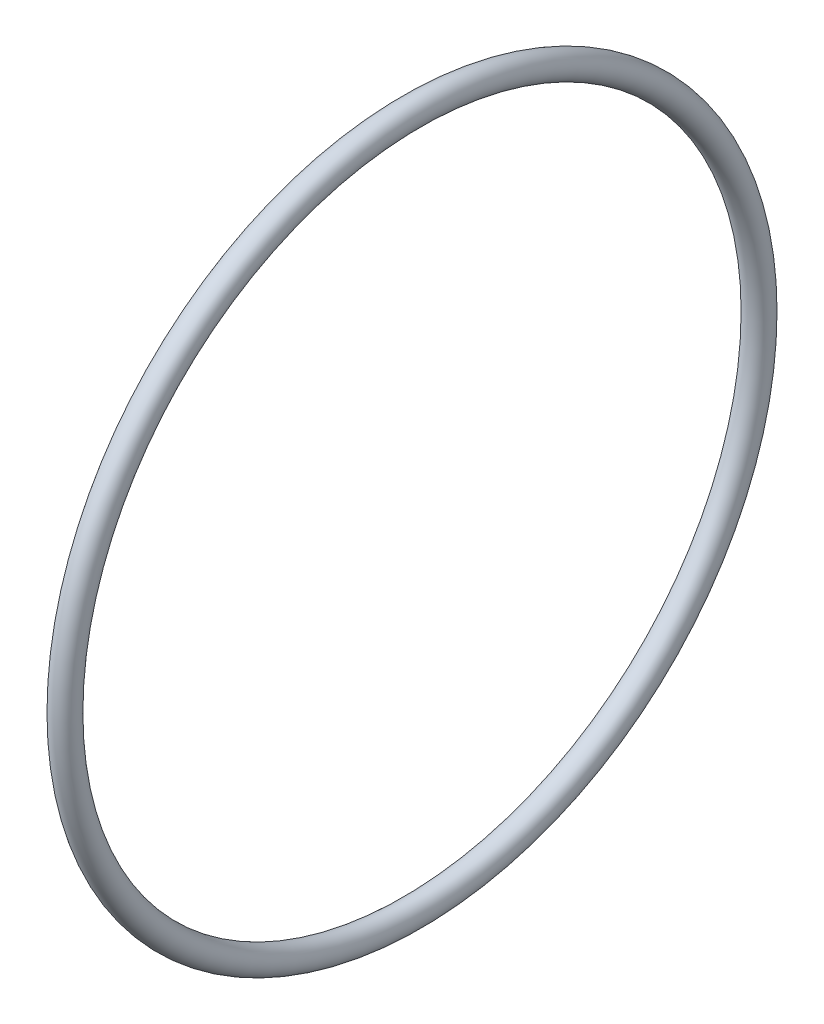
SolidWorks part; units mm, degrees
ref_plane "Front Plane" through (0, 0, 0) normal (0, 0, 1) x (1, 0, 0)
ref_plane "Top Plane" through (0, 0, 0) normal (0, 1, 0) x (1, 0, 0)
ref_plane "Right Plane" through (0, 0, 0) normal (1, 0, 0) x (0, 0, -1)
sketch "Sketch2" plane through (0, 0, 0) normal (0, 0, 1) x (1, 0, 0)
  line L0 (0, 0) -> (58.591, 0) construction
  line L2 (0, 0) -> (18.4, 0)
  line L3 (0, 0) -> (0, 2.5)
  line L4 (0, 2.5) -> (18.4, 2.5)
  line L5 (18.4, 0) -> (18.4, 2.5)
  line L6 (6.0094, 2.5) -> (6.0094, 6)
  line L11 (6.0094, 6) -> (9.9794, 6)
  line L16 (12.9794, 6) -> (12.9794, 3)
  line L17 (12.9794, 3) -> (13.6398, 3)
  line L18 (13.6398, 3) -> (13.6398, 2.5)
  line L19 (13.6398, 2.5) -> (6.0094, 2.5)
  line L22 (13.6398, 2.5) -> (16.1198, 2.5)
  line L23 (13.6398, 2.5) -> (13.6398, 4)
  line L24 (13.6398, 4) -> (16.1198, 4)
  line L25 (16.1198, 2.5) -> (16.1198, 4)
  line L27 (6.0094, 6) -> (9.9794, 6)
  line L28 (6.0094, 6) -> (6.0094, 9)
  line L29 (6.0094, 9) -> (9.9794, 9)
  line L30 (9.9794, 6) -> (9.9794, 9)
  line L31 (6.0094, 9) -> (6.0094, 8.25)
  line L32 (6.0094, 8.25) -> (5.0094, 8.25)
  line L33 (8.6609, 22.001) -> (8.6609, 12.476) construction
  line L34 (5.0094, 12.476) -> (12.3124, 12.476)
  line L35 (9.9794, 9) -> (12.3124, 9)
  line L36 (5.0094, 7.9375) -> (1.8344, 7.9375)
  line L37 (5.0094, 8.25) -> (5.0094, 12.476)
  line L38 (5.0094, 7.9375) -> (5.0094, 13.9365)
  line L39 (5.0094, 13.9365) -> (1.8344, 13.9365)
  line L40 (1.8344, 7.9375) -> (1.8344, 13.9365)
  line L41 (5.0094, 22.001) -> (12.3124, 22.001)
  line L42 (5.0094, 22.001) -> (5.0094, 30.1625)
  line L43 (5.0094, 30.1625) -> (12.3124, 30.1625)
  line L44 (12.3124, 22.001) -> (12.3124, 30.1625)
  line L49 (16.6398, 22.001) -> (16.6398, 7.5)
  line L51 (23.0198, 7.5) -> (23.0198, 6.5)
  line L54 (16.1198, 4) -> (13.6398, 4)
  line L56 (18.0398, 7.5) -> (23.0198, 7.5)
  line L57 (13.3124, 22.001) -> (16.6398, 22.001)
  line L58 (16.1198, 3.5) -> (20.0198, 3.5)
  line L59 (29.9098, 14) -> (26.9098, 11)
  line L60 (4.0094, 31.75) -> (18.0398, 31.75)
  line L61 (18.0398, 7.5) -> (23.0198, 7.5)
  line L62 (18.0398, 7.5) -> (18.0398, 12)
  line L63 (18.0398, 12) -> (23.0198, 12)
  line L64 (23.0198, 7.5) -> (23.0198, 12)
  line L65 (18.0398, 31.75) -> (18.0398, 12)
  line L66 (23.0198, 11) -> (26.9098, 11)
  line L67 (34.8098, 23) -> (31.3098, 19.5)
  line L68 (35.8098, 31) -> (38.7998, 33.99)
  line L69 (29.9098, 14) -> (29.9098, 15)
  line L70 (29.9098, 15) -> (22.9398, 15)
  line L71 (22.9398, 15) -> (21.0398, 15)
  line L72 (18.0398, 7.5) -> (16.6398, 7.5)
  line L73 (21.0398, 15) -> (21.0398, 43)
  line L74 (19.5798, 40) -> (9.6198, 40)
  line L75 (9.6198, 40) -> (4.0094, 40)
  line L76 (21.0398, 43) -> (19.5798, 43)
  line L77 (22.9398, 15) -> (29.9098, 15)
  line L78 (22.9398, 15) -> (22.9398, 21)
  line L79 (22.9398, 21) -> (29.9098, 21)
  line L80 (29.9098, 15) -> (29.9098, 21)
  line L81 (9.6198, 40) -> (19.5798, 40)
  line L82 (9.6198, 40) -> (9.6198, 50)
  line L83 (9.6198, 50) -> (19.5798, 50)
  line L84 (19.5798, 40) -> (19.5798, 50)
  line L85 (4.0094, 40) -> (4.0094, 31.75)
  line L86 (12.9794, 3) -> (12.9794, 2.5)
  line L87 (31.3098, 19.5) -> (29.9098, 19.5)
  line L88 (21.4694, 63.5) -> (21.4694, 51.308)
  line L89 (21.4694, 63.5) -> (25.9398, 63.5)
  line L90 (25.9398, 63.5) -> (25.9398, 25)
  line L91 (27.8398, 25) -> (25.9398, 25)
  line L92 (9.6198, 48) -> (8.1598, 48)
  line L93 (8.1598, 48) -> (8.1598, 53.476)
  line L94 (8.1598, 53.476) -> (19.5798, 53.476)
  line L95 (19.5798, 53.476) -> (19.5798, 50)
  line L96 (13.8698, 63.001) -> (13.8698, 53.476) construction
  line L97 (8.1598, 63.001) -> (19.5798, 63.001)
  line L98 (8.1598, 63.001) -> (8.1598, 68.2625)
  line L99 (8.1598, 68.2625) -> (19.5798, 68.2625)
  line L100 (19.5798, 63.001) -> (19.5798, 68.2625)
  line L101 (12.9794, 6) -> (11.9794, 6)
  line L102 (8.1598, 44.825) -> (4.9848, 44.825)
  line L103 (8.1598, 44.825) -> (8.1598, 54.9365)
  line L104 (8.1598, 54.9365) -> (4.9848, 54.9365)
  line L106 (9.9794, 6) -> (10.8794, 6)
  line L107 (27.8398, 25) -> (34.8098, 25)
  line L108 (34.8098, 25) -> (34.8098, 23)
  line L109 (0, 0) -> (-2, 0)
  line L110 (0, 0) -> (0, 11)
  line L111 (27.8398, 25) -> (34.8098, 25)
  line L112 (27.8398, 25) -> (27.8398, 32.5)
  line L113 (27.8398, 32.5) -> (34.8098, 32.5)
  line L114 (34.8098, 25) -> (34.8098, 32.5)
  line L115 (35.8098, 31) -> (34.8098, 31)
  line L116 (27.8398, 32.5) -> (27.8398, 64.5)
  line L117 (20.5373, 74.025) -> (6.2023, 74.025)
  line L118 (6.2023, 74.025) -> (6.2023, 76.2)
  line L119 (38.7998, 47.29) -> (30.8398, 55.25)
  line L120 (0, 11) -> (-2, 11)
  line L121 (38.7998, 43.815) -> (30.8623, 43.815)
  line L123 (-4.8152, 69.85) -> (1.5348, 76.2)
  line L124 (38.7998, 47.29) -> (38.7998, 33.99)
  line L125 (-2, 0) -> (-2, 11)
  line L126 (38.7998, 37.465) -> (30.8623, 37.465)
  line L127 (30.8623, 43.815) -> (30.8623, 37.465)
  line L128 (6.0094, 2.5) -> (6.0094, 0)
  line L129 (-0.0152, 63.5) -> (-0.0152, 30)
  line L132 (4.9848, 63.5) -> (-0.0152, 63.5)
  line L136 (-1.8152, 30) -> (-11.7752, 30)
  line L138 (-13.7752, 25.4) -> (-2, 25.4)
  line L139 (-2, 25.4) -> (-2, 11.5)
  line L140 (27.8398, 64.5) -> (20.5373, 64.5)
  line L141 (-1.8152, 30) -> (-11.7752, 30)
  line L142 (-1.8152, 30) -> (-1.8152, 39)
  line L143 (-1.8152, 39) -> (-11.7752, 39)
  line L144 (-11.7752, 30) -> (-11.7752, 39)
  line L145 (20.5373, 64.5) -> (20.5373, 74.025)
  line L146 (-12.7752, 37) -> (-12.7752, 47.29)
  line L147 (-12.7752, 37) -> (-11.7752, 37)
  line L148 (30.8398, 55.25) -> (30.8398, 76.2)
  line L149 (11.9794, 6) -> (11.9794, 5.45)
  line L154 (-2, 11.5) -> (0.5, 11.5)
  line L155 (4.9848, 60.6197) -> (24.0348, 60.6197)
  line L160 (4.9848, 60.6197) -> (4.9848, 55.8572)
  line L161 (4.9848, 55.8572) -> (24.0348, 55.8572)
  line L166 (24.0348, 60.6197) -> (24.0348, 55.8572)
  line L167 (4.9848, 60.6197) -> (24.0348, 55.8572) construction
  line L172 (4.9848, 55.8572) -> (24.0348, 60.6197) construction
  line L173 (24.0348, 62.2072) -> (25.9398, 62.2072)
  line L174 (11.9794, 5.45) -> (10.8794, 5.45)
  line L175 (10.8794, 6) -> (10.8794, 5.45)
  line L176 (24.0348, 62.2072) -> (24.0348, 54.2697)
  line L177 (24.0348, 54.2697) -> (25.9398, 54.2697)
  line L178 (25.9398, 62.2072) -> (25.9398, 54.2697)
  line L179 (24.0348, 62.2072) -> (25.9398, 54.2697) construction
  line L180 (24.0348, 54.2697) -> (25.9398, 62.2072) construction
  line L181 (3, 19.6197) -> (15.7, 19.6197)
  line L182 (3, 19.6197) -> (3, 14.8572)
  line L183 (3, 14.8572) -> (15.7, 14.8572)
  line L184 (15.7, 19.6197) -> (15.7, 14.8572)
  line L185 (3, 19.6197) -> (15.7, 14.8572) construction
  line L186 (3, 14.8572) -> (15.7, 19.6197) construction
  line L187 (15.7, 21.2072) -> (16.6398, 21.2072)
  line L188 (15.7, 21.2072) -> (15.7, 13.2697)
  line L189 (15.7, 13.2697) -> (16.6398, 13.2697)
  line L190 (16.6398, 21.2072) -> (16.6398, 13.2697)
  line L191 (15.7, 21.2072) -> (16.6398, 13.2697) construction
  line L192 (15.7, 13.2697) -> (16.6398, 21.2072) construction
  line L193 (0.5, 11.5) -> (0.5, 6.9375)
  line L194 (0.5, 6.9375) -> (1.8344, 6.9375)
  line L195 (23.0198, 6.5) -> (20.0198, 3.5)
  line L196 (4.9848, 63.5) -> (4.9848, 54.9365)
  line L197 (3, 43.825) -> (4.9848, 43.825)
  line L198 (1.8344, 6.9375) -> (1.8344, 7.9375)
  line L199 (6.0094, 0) -> (12.9794, 0)
  line L200 (12.9794, 0) -> (12.9794, 2.5)
  line L201 (18.0398, 31.75) -> (18.0398, 35.875)
  line L202 (18.0398, 35.875) -> (21.0398, 35.875)
  line L203 (30.8398, 76.2) -> (6.2023, 76.2)
  line L204 (2.7573, 69.85) -> (7.2023, 69.85) construction
  line L205 (7.2023, 67.4688) -> (26.2523, 67.4688)
  line L206 (7.2023, 74.025) -> (7.2023, 64.5)
  line L207 (7.2023, 64.5) -> (-1.8152, 64.5)
  line L208 (-1.8152, 64.5) -> (-1.8152, 39)
  line L209 (-12.7752, 47.29) -> (-4.8152, 55.25)
  line L210 (-4.8152, 55.25) -> (-4.8152, 69.85)
  line L211 (7.2023, 67.4688) -> (7.2023, 72.2312)
  line L212 (7.2023, 72.2312) -> (26.2523, 72.2313)
  line L213 (26.2523, 67.4688) -> (26.2523, 72.2313)
  line L214 (26.2523, 73.8187) -> (30.8398, 73.8187)
  line L215 (26.2523, 73.8187) -> (26.2523, 65.8813)
  line L216 (26.2523, 65.8813) -> (30.8398, 65.8813)
  line L217 (30.8398, 73.8187) -> (30.8398, 65.8813)
  line L218 (2.7573, 72.2313) -> (24.9823, 72.2313)
  line L219 (2.7573, 72.2313) -> (2.7573, 67.4687)
  line L220 (2.7573, 67.4687) -> (24.9823, 67.4687)
  line L221 (24.9823, 72.2313) -> (24.9823, 67.4687)
  line L222 (24.9823, 69.85) -> (20.5373, 69.85) construction
  line L223 (21.4694, 51.308) -> (22.9398, 51.308)
  line L224 (22.9398, 51.308) -> (22.9398, 21)
  line L225 (13.6398, 4) -> (13.6398, 12.2697)
  line L226 (13.6398, 12.2697) -> (13.3124, 12.2697)
  line L227 (13.3124, 12.2697) -> (13.3124, 22.001)
  line L228 (12.3124, 9) -> (12.3124, 12.476)
  line L229 (-1.8152, 30) -> (-0.0152, 30)
  line L230 (8.1598, 65.6317) -> (2.7573, 65.6317) construction
  line L231 (19.5798, 65.6317) -> (24.9823, 65.6317) construction
  line L232 (1.5348, 76.2) -> (6.2023, 76.2)
  line L233 (-11.7752, 30) -> (-13.7752, 30)
  line L234 (-13.7752, 30) -> (-13.7752, 25.4)
  line L235 (3, 13.9365) -> (3, 43.825)
  line L236 (4.9848, 54.9365) -> (4.9848, 44.825)
  line L237 (4.9848, 43.825) -> (4.9848, 44.825)
  circle A0 centre (26.8898, 25.95) radius 0.95
  circle A1 centre (21.9898, 15.95) radius 0.95
  circle A2 centre (17.3398, 8.2) radius 0.7
  circle A3 centre (10.4294, 6.45) radius 0.45
  circle A4 centre (-0.9152, 30.9) radius 0.9
  point P7 (24.9873, 58.2385)
  point P131 (16.1699, 17.2385)
  point P135 (14.5098, 58.2385)
  point P146 (9.35, 17.2385)
sketch "Sketch3" plane through (0, 0, 0) normal (0, 0, 1) x (1, 0, 0)
  circle A0 centre (26.8898, 25.95) radius 0.95 construction
  circle A1 centre (26.8898, 25.95) radius 0.95
revolve "Revolve1" add sketch "Sketch3" angle 360 about L0
